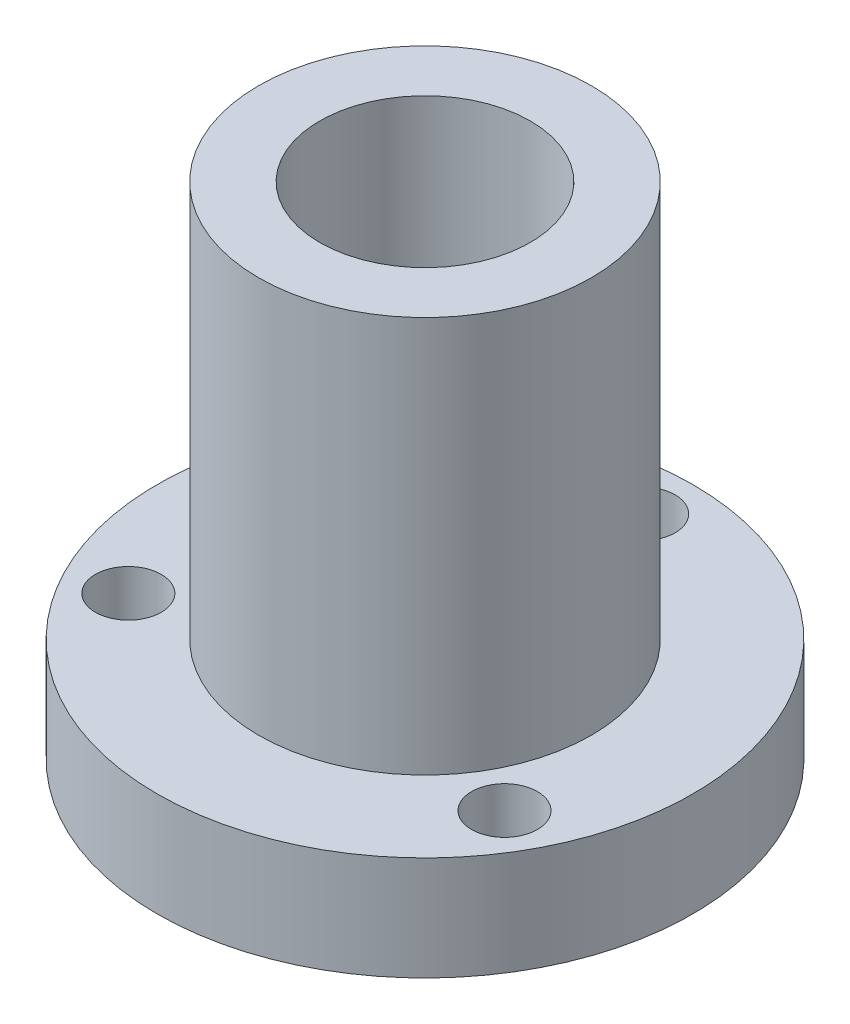
SolidWorks part; units mm, degrees
material "Brass"
ref_plane "Front Plane" through (0, 0, 0) normal (0, 0, 1) x (1, 0, 0)
ref_plane "Top Plane" through (0, 0, 0) normal (0, 1, 0) x (1, 0, 0)
ref_plane "Right Plane" through (0, 0, 0) normal (1, 0, 0) x (0, 0, -1)
sketch "Sketch1" plane through (0, 0, 0) normal (0, 1, 0) x (1, 0, 0)
  circle A0 centre (0, 0) radius 4
  circle A1 centre (0, 0) radius 10.175
  dimension "D1" = 8
  dimension "D2" = 20.35
extrude "Boss-Extrude1" add sketch "Sketch1" along normal blind 3.95
sketch "Sketch2" plane through (0, 3.95, 0) normal (0, 1, 0) x (1, 0, 0)
  circle A0 centre (0, 0) radius 6.32
  circle A1 centre (0, 0) radius 4 construction
  circle A2 centre (0, 0) radius 4
  dimension "D1" = 12.64
extrude "Boss-Extrude2" add sketch "Sketch2" along normal offset from surface (15.05 mm away) 19 up to face at (0, 0, 10.175)
sketch "Sketch3" plane through (0, 0, 0) normal (0, -1, 0) x (1, 0, 0)
  circle A0 centre (0, 0) radius 8.25 construction
  circle A1 centre (0, -8.25) radius 1.6
  circle A2 centre (-7.1447, 4.125) radius 1.6
  circle A3 centre (7.1447, 4.125) radius 1.6
  point P11 (0, 0)
  dimension "D1" = 3.2
  dimension "D3" = 16.5
  dimension "D2" = 3
hole_wizard "Tap Drill for M3 Tap1" positions "3DSketch1" profile "Sketch4" hole size "M3" standard "DIN" end condition up to next
sketch3d "3DSketch1"
  point P0 (-7.1447, 0, 4.125)
  point P3 (7.1447, 0, 4.125)
  point P6 (0, 0, -8.25)
sketch "Sketch4" plane through (-7.1447, 0, 4.125) normal (1, 0, 0) x (0, 0, -1)
  line L0 (0, 0) -> (0, 3.95)
  line L1 (0, 3.95) -> (1.25, 3.95)
  line L2 (1.25, 3.95) -> (1.25, 0)
  line L5 (1.25, 0) -> (0, 0)
  line L11 (0, -6.35) -> (0, 107.95) construction
  dimension "Thru Hole Dia." = 2.5
  dimension "Thru Hole Depth" = 3.95
